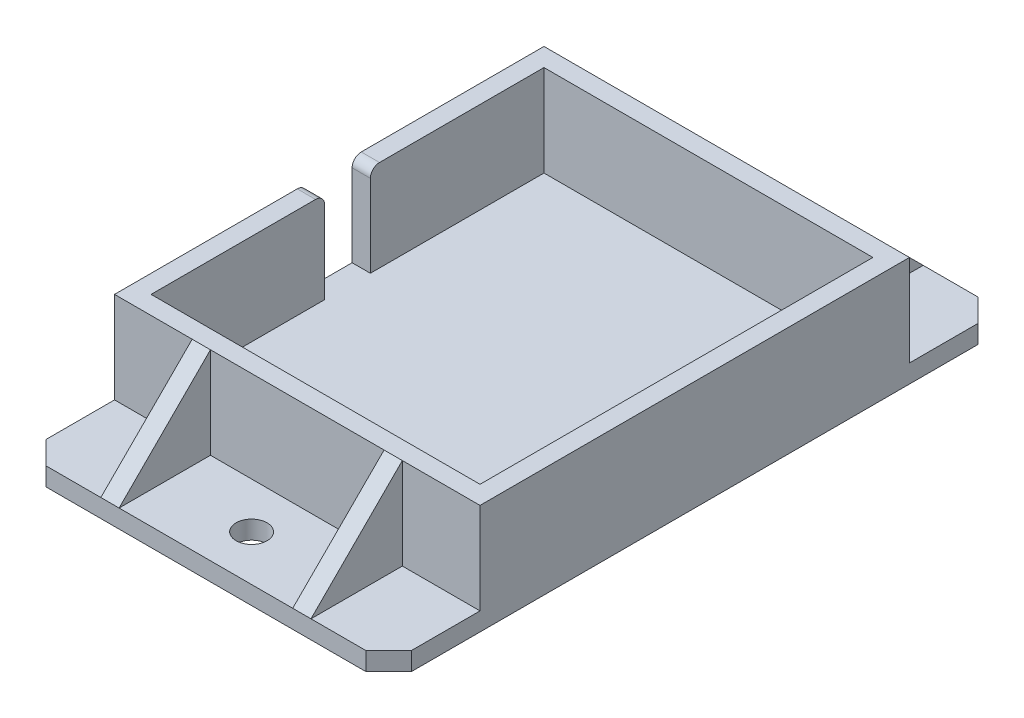
SolidWorks part; units mm, degrees
ref_plane "Front Plane" through (0, 0, 0) normal (0, 0, 1) x (1, 0, 0)
ref_plane "Top Plane" through (0, 0, 0) normal (0, 1, 0) x (1, 0, 0)
ref_plane "Right Plane" through (0, 0, 0) normal (1, 0, 0) x (0, 0, -1)
sketch "Sketch1" plane through (0, 0, 0) normal (0, 1, 0) x (1, 0, 0)
  line L5 (-40, 47) -> (40, 47)
  line L6 (-36, 43) -> (36, 43)
  line L10 (-36, 43) -> (-36, -43)
  line L11 (-36, -43) -> (36, -43)
  line L12 (36, 43) -> (36, -43)
  line L13 (-36, 43) -> (36, -43) construction
  line L14 (-36, -43) -> (36, 43) construction
  line L15 (40, 47) -> (40, -47)
  line L16 (-40, -47) -> (40, -47)
  line L17 (-40, 47) -> (-40, -47)
  point P0 (0, 0)
  dimension "D1" = 86
  dimension "D2" = 72
  dimension "D3" = 4
extrude "Boss-Extrude3" add sketch "Sketch1" along normal blind 20
sketch "Sketch10" plane through (0, 0, 0) normal (0, -1, 0) x (1, 0, 0)
  line L11 (-40, -47) -> (-40, 47) construction
  line L12 (0, 0) -> (-46.4736, 0) construction
  line L18 (-40, -67) -> (40, -67)
  line L19 (-40, -67) -> (-40, 67)
  line L20 (-40, 67) -> (40, 67)
  line L21 (40, -67) -> (40, 67)
  line L22 (-40, -67) -> (40, 67) construction
  line L23 (-40, 67) -> (40, -67) construction
  line L24 (-40, 47) -> (40, 47) construction
  point P0 (0, 0)
  point P11 (0, 57)
  point P16 (0, -57)
  dimension "D1" = 20
  dimension "D2" = 10
extrude "Boss-Extrude4" add sketch "Sketch10" along normal blind 4
sketch "Sketch11" plane through (-40, 0, 0) normal (-1, 0, 0) x (0, 0, 1)
  line L0 (0, 0) -> (0, 37.1567) construction
  line L1 (5, 20) -> (5, 0)
  line L2 (-47, 20) -> (47, 20) construction
  line L3 (5, 0) -> (-5, 0)
  line L4 (-5, 0) -> (-5, 20)
  line L5 (-5, 20) -> (5, 20)
  dimension "D1" = 5
  dimension "D2" = 10
extrude "Cut-Extrude1" cut sketch "Sketch11" against normal up to next
fillet "Fillet2" radius 2 2 edges at (-38, 20, -5) (-38, 20, 5)
sketch "Sketch24" plane through (0, 0, 0) normal (0, 1, 0) x (1, 0, 0)
  point P0 (0, 57)
  point P2 (0, -57)
hole_wizard "Tap Drill for M8 Tap2" positions "3DSketch4" profile "Sketch25" hole size "M8" standard "ISO" end condition through all
sketch3d "3DSketch4"
  point P0 (0, 0, 57)
  point P3 (0, 0, -57)
sketch "Sketch25" plane through (0, 0, 57) normal (1, 0, 0) x (0, 0, 1)
  line L0 (0, 0) -> (0, 4)
  line L1 (0, 4) -> (3.4, 4)
  line L2 (3.4, 4) -> (3.4, 0)
  line L5 (3.4, 0) -> (0, 0)
  line L11 (0, -6.35) -> (0, 107.95) construction
  dimension "Thru Hole Dia." = 6.8
  dimension "Thru Hole Depth" = 4
ref_plane "Plane5" through (-21, 0, 0) normal (-1, 0, 0) x (0, 0, 1)
sketch "Sketch26" plane through (-21, 0, 0) normal (-1, 0, 0) x (0, 0, 1)
  line L0 (-67, 0) -> (-47, 20)
rib "Rib10" sketch "Sketch26" sketch "Sketch26" thickness 4 extrusion direction parallel to sketch draft on no parameters "D1"=4
mirror "Mirror3" about plane through (0, 0, 0) normal (1, 0, 0) of "Rib10"
mirror "Mirror4" about plane through (0, 0, 0) normal (0, 0, 1) of "Rib10", "Mirror3"
chamfer "Chamfer1" distance 5 angle 45 4 edges at (40, -2, 67) (-40, -2, 67) (40, -2, -67) (-40, -2, -67)
